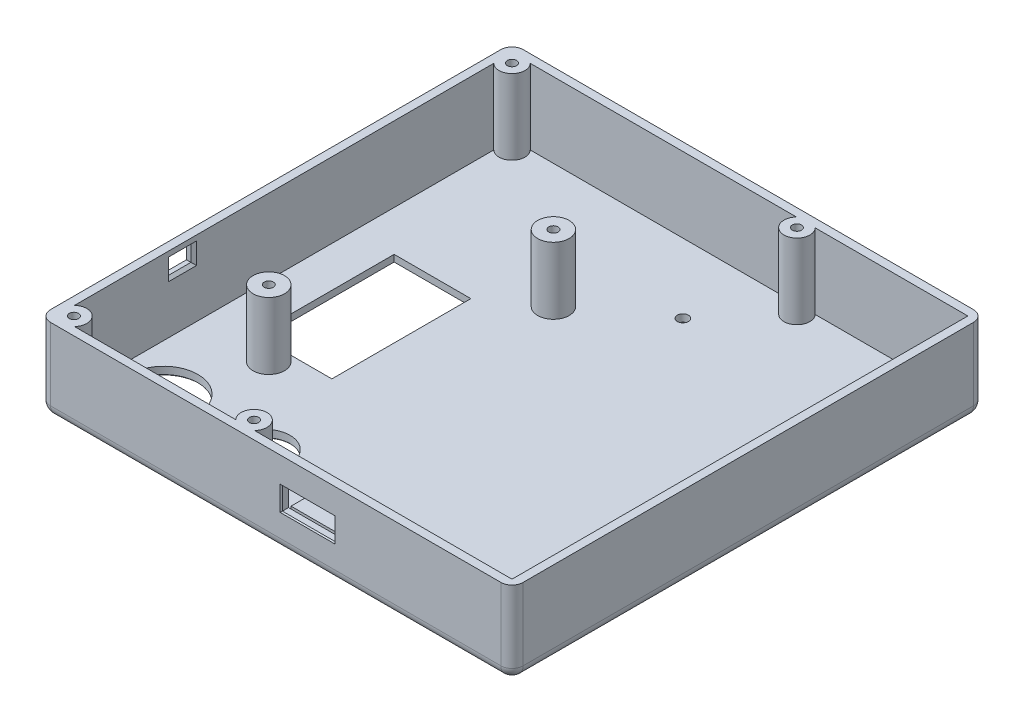
SolidWorks part; units mm, degrees
material "PLA"
ref_plane "前视基准面" through (0, 0, 0) normal (0, 0, 1) x (1, 0, 0)
ref_plane "上视基准面" through (0, 0, 0) normal (0, 1, 0) x (1, 0, 0)
ref_plane "右视基准面" through (0, 0, 0) normal (1, 0, 0) x (0, 0, -1)
sketch "草图1" plane through (0, 0, 0) normal (0, 1, 0) x (1, 0, 0)
  line L1 (-42.5, 42.5) -> (42.5, 42.5)
  line L2 (-42.5, 42.5) -> (-42.5, -42.5)
  line L3 (-42.5, -42.5) -> (42.5, -42.5)
  line L4 (42.5, 42.5) -> (42.5, -42.5)
  line L5 (-42.5, 42.5) -> (42.5, -42.5) construction
  line L6 (-42.5, -42.5) -> (42.5, 42.5) construction
  point P0 (0, 0)
  dimension "D1" = 85
  dimension "D2" = 85
extrude "凸台-拉伸1" add sketch "草图1" along normal blind 15
shell "抽壳1" thickness 1.5 removed face at (0, 15, 0)
fillet "圆角1" radius 2 4 edges at (0, 0, 42.5) (-42.5, 0, 0) (42.5, 0, 0) (0, 0, -42.5)
fillet "圆角2" radius 2 8 edges at (-41.9142, 0.5858, -41.9142) (-41.9142, 0.5858, 41.9142) (41.9142, 0.5858, 41.9142) (41.9142, 0.5858, -41.9142) (-42.5, 8.5, -42.5) (-42.5, 8.5, 42.5) (42.5, 8.5, 42.5) (42.5, 8.5, -42.5)
sketch "草图16" plane through (0, 0, 42.5) normal (0, 0, 1) x (1, 0, 0)
  line L1 (1, 6.25) -> (10.5, 6.25)
  line L2 (1, 6.25) -> (1, 10.25)
  line L3 (1, 10.25) -> (10.5, 10.25)
  line L4 (10.5, 6.25) -> (10.5, 10.25)
  line L7 (10.25, 7) -> (10.25, 11) construction
  line L8 (1.25, 7) -> (1.25, 11) construction
  line L9 (10.25, 10) -> (1.25, 10) construction
  line L10 (9.75, 6.5) -> (1.75, 6.5) construction
  dimension "D1" = 0.25
  dimension "D2" = 0.25
  dimension "D3" = 0.25
  dimension "D4" = 0.25
extrude "充电口切除-拉伸7" cut sketch "草图16" against normal up to next
sketch "草图3" plane through (0, 0, 0) normal (0, -1, 0) x (1, 0, 0)
  line L6 (14.5, 41) -> (10.25, 41) construction
  line L17 (14.5, 13) -> (14.5, 41) construction
  circle A0 centre (13.0023, 32.5) radius 1.9
  dimension "D1" = 3.8
  dimension "D2" = 8.5
  dimension "D3" = 1.4977
extrude "充电灯切除-拉伸2" cut sketch "草图3" against normal up to next
sketch "草图4" plane through (0, 0, 0) normal (0, -1, 0) x (1, 0, 0)
  circle A2 centre (-32.65, 30) radius 6.15
  circle A3 centre (-32.65, 30) radius 5.85 construction
  circle A4 centre (-32.65, 30) radius 5.85 construction
extrude "按钮切除-拉伸3" cut sketch "草图4" against normal up to next
chamfer "充电口灯倒角1" distance 0.2 angle 45 9 edges at (10.5, 8.25, 41) (5.75, 6.25, 41) (5.75, 10.25, 41) (1, 8.25, 41) (10.5, 8.25, 42.5) (5.75, 6.25, 42.5) (5.75, 10.25, 42.5) (1, 8.25, 42.5) (13.0023, 1.5, 34.4)
sketch "草图5" plane through (-42.5, 0, 0) normal (-1, 0, 0) x (0, 0, 1)
  line L1 (16.25, 13.57) -> (20.25, 13.57)
  line L2 (16.25, 13.57) -> (16.25, 10.73)
  line L3 (16.25, 10.73) -> (20.25, 10.73)
  line L4 (20.25, 13.57) -> (20.25, 10.73)
  line L5 (18.25, 12.57) -> (16.45, 12.57) construction
  line L6 (18.25, 10.93) -> (20.05, 10.93) construction
  line L8 (20.05, 10.93) -> (20.05, 12.57) construction
  line L9 (16.45, 12.57) -> (16.45, 10.93) construction
  dimension "D1" = 0.2
  dimension "D2" = 1
  dimension "D3" = 0.2
  dimension "D4" = 0.2
extrude "开关切除-拉伸4" cut sketch "草图5" against normal up to next
chamfer "开关倒角3" distance 0.2 angle 45 4 edges at (-42.5, 12.15, 20.25) (-42.5, 10.73, 18.25) (-42.5, 12.15, 16.25) (-42.5, 13.57, 18.25)
chamfer "开关倒角4" distance 0.5 angle 45 4 edges at (-41, 12.15, 20.25) (-41, 10.73, 18.25) (-41, 12.15, 16.25) (-41, 13.57, 18.25)
sketch "草图6" plane through (0, 0, 0) normal (0, -1, 0) x (1, 0, 0)
  line L5 (-19.9, 12.5) -> (-33.7, 12.5)
  line L6 (-33.7, 12.5) -> (-33.7, -12.5)
  line L7 (-19.9, -12.5) -> (-33.7, -12.5)
  line L8 (-19.9, 12.5) -> (-19.9, -12.5)
  line L9 (40.5, 40.5) -> (-40.5, 40.5) construction
  line L10 (-40.5, 40.5) -> (-40.5, -40.5) construction
  dimension "D1" = 13.8
  dimension "D2" = 25
  dimension "D3" = 28
  dimension "D4" = 6.8
extrude "屏幕切除-拉伸6" cut sketch "草图6" against normal up to next
chamfer "屏幕倒角6" distance 0.3 angle 45 4 edges at (-26.8, 0, 12.5) (-33.7, 0, 0) (-26.8, 0, -12.5) (-19.9, 0, 0)
sketch "草图7" plane through (0, 0, 0) normal (0, -1, 0) x (1, 0, 0)
  line L4 (40.5, 40.5) -> (-40.5, 40.5)
  line L6 (40.5, 40.5) -> (-40.5, 40.5)
  line L8 (-40.5, 40.5) -> (-40.5, -40.5)
  line L10 (-40.5, 40.5) -> (-40.5, -40.5)
  line L12 (-40.5, -40.5) -> (40.5, -40.5)
  line L13 (-40.5, -40.5) -> (40.5, -40.5)
  line L14 (40.5, -40.5) -> (40.5, 40.5)
  line L15 (40.5, -40.5) -> (40.5, 40.5)
  circle A0 centre (-14.8774, 29.5) radius 4.25 construction
  circle A1 centre (-14.8774, 29.5) radius 4.25 construction
  circle A3 centre (-14.8774, 29.5) radius 4.45
  dimension "D1" = 0
extrude "人体切除-拉伸7" cut sketch "草图7" against normal up to next contours A3
sketch "草图9" plane through (0, 0, 0) normal (0, -1, 0) x (1, 0, 0)
  circle A0 centre (2.2382, -28.5) radius 1
extrude "蜂鸣切除-拉伸8" cut sketch "草图9" against normal up to next
chamfer "蜂鸣倒角7" distance 0.2 angle 45 3 edges at (2.2382, 0, -29.5) (-32.65, 0, 23.85) (-14.8774, 0, 25.05)
sketch "草图10" plane through (0, 1.5, 0) normal (0, 1, 0) x (1, 0, 0)
  line L0 (41, 41) -> (-41, 41) construction
  line L1 (-41, 41) -> (-41, -41) construction
  line L2 (-41, -41) -> (41, -41) construction
  line L3 (8.85, 37.5) -> (8.85, 36.5) construction
  line L4 (-3, -41) -> (-3, -13) construction
  line L6 (-41, -41) -> (41, -41) construction
  circle A0 centre (-39.4, 39.4) radius 0.825
  circle A1 centre (-39.4, -39.4) radius 0.825
  circle A2 centre (-7, -39.4) radius 0.825
  circle A3 centre (11.85, 39.4) radius 0.825
  dimension "D1" = 1.65
  dimension "D6" = 3
  dimension "D2" = 1.6
  dimension "D3" = 1.6
  dimension "D4" = 1.6
  dimension "D5" = 1.6
  dimension "D7" = 1.6
  dimension "D8" = 4
  dimension "D9" = 1.6
extrude "四角固定拉伸-薄壁1" add sketch "草图10" along normal up to surface (13.5 mm away) thin thin type one direction wall 1.5
sketch "草图12" plane through (0, 1.5, 0) normal (0, 1, 0) x (1, 0, 0)
  line L1 (-12, -12.5) -> (-39, -12.5) construction
  line L2 (-24.75, -15.3977) -> (-24.75, -20.3977) construction
  circle A0 centre (-28.25, -15.5) radius 2.825
  circle A1 centre (-11.25, 18.7) radius 2.825
  circle A2 centre (-28.25, -15.5) radius 0.825
  circle A3 centre (-11.25, 18.7) radius 0.825
  circle A4 centre (-11.25, 18.7) radius 1 construction
  dimension "D1" = 2
  dimension "D4" = 2
  dimension "D7" = 1.65
  dimension "D8" = 1.65
  dimension "D2" = 3
  dimension "D3" = 3.5
extrude "压板固定凸台-拉伸2" add sketch "草图12" along normal up to surface (12 mm away)
sketch "草图14" plane through (42.5, 0, 0) normal (1, 0, 0) x (0, 0, -1)
  line L0 (40.5, 0) -> (-40.5, 0) construction
  line L1 (10, 0) -> (15, 0)
  line L2 (10, 0) -> (10, 5)
  line L3 (10, 5) -> (15, 5)
  line L4 (15, 0) -> (15, 5)
  line L5 (0, 0) -> (0, 15) construction
  line L6 (-40.5, 15) -> (40.5, 15) construction
  line L7 (-15, 0) -> (-15, 5)
  line L8 (-10, 5) -> (-15, 5)
  line L9 (-10, 0) -> (-10, 5)
  line L10 (-10, 0) -> (-15, 0)
  dimension "D1" = 5
  dimension "D2" = 5
  dimension "D3" = 10
extrude "电池顶凸台-拉伸3" add sketch "草图14" against normal blind 3.9 from surface starting at face at (41, 8.25, 0)
sketch "草图15" plane through (0, 1.5, 0) normal (0, 1, 0) x (1, 0, 0)
  line L1 (1.25, -41) -> (10.25, -41)
  line L2 (1.25, -41) -> (1.25, -37)
  line L3 (1.25, -37) -> (10.25, -37)
  line L4 (10.25, -41) -> (10.25, -37)
extrude "充电板凸台-拉伸4" add sketch "草图15" along normal up to surface (5 mm away)
sketch "草图17" plane through (0, 0, 0) normal (0, -1, 0) x (-1, 0, 0)
  text T0 "<b>HGH</b>" font "黑体" height 5
extrude "名字切除-拉伸1" cut sketch "草图17" against normal blind 0.2
